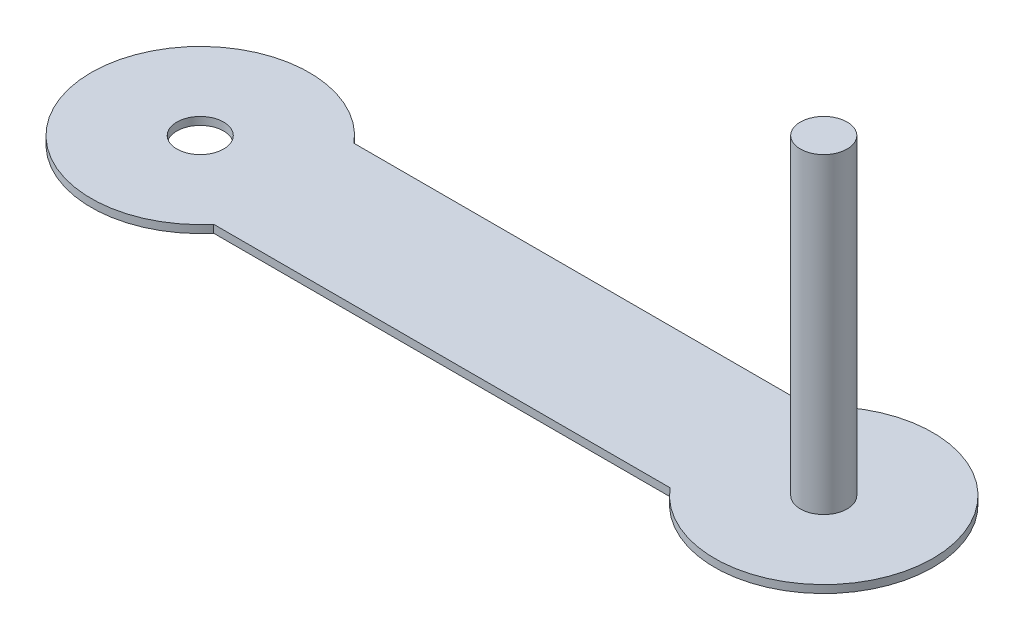
SolidWorks part; units mm, degrees
ref_plane "Front Plane" through (0, 0, 0) normal (0, 0, 1) x (1, 0, 0)
ref_plane "Top Plane" through (0, 0, 0) normal (0, 1, 0) x (1, 0, 0)
ref_plane "Right Plane" through (0, 0, 0) normal (1, 0, 0) x (0, 0, -1)
sketch "Sketch1" plane through (0, 0, 0) normal (0, 1, 0) x (1, 0, 0)
  line L0 (92.9519, 28.575) -> (-92.9519, 28.575)
  line L1 (-92.9519, -28.575) -> (92.9519, -28.575)
  line L3 (-149.117, 0) -> (199.2814, 0) construction
  arc A0 (92.9519, -28.575) -> (92.9519, 28.575) centre (127, 0) ccw
  arc A1 (-92.9519, -28.575) -> (-92.9519, 28.575) centre (-127, 0) cw
  circle A2 centre (-127, 0) radius 9.525
  dimension "D1" = 44.45
  dimension "D3" = 44.45
  dimension "D6" = 28.575
  dimension "D8" = 19.05
  dimension "D2" = 57.15
  dimension "D4" = 127
  dimension "D5" = 127
extrude "Boss-Extrude1" add sketch "Sketch1" along normal blind 3.175
sketch "Sketch2" plane through (0, 3.175, 0) normal (0, 1, 0) x (1, 0, 0)
  circle A0 centre (127, 0) radius 9.525
  dimension "D1" = 19.05
extrude "Boss-Extrude2" add sketch "Sketch2" along normal blind 127
